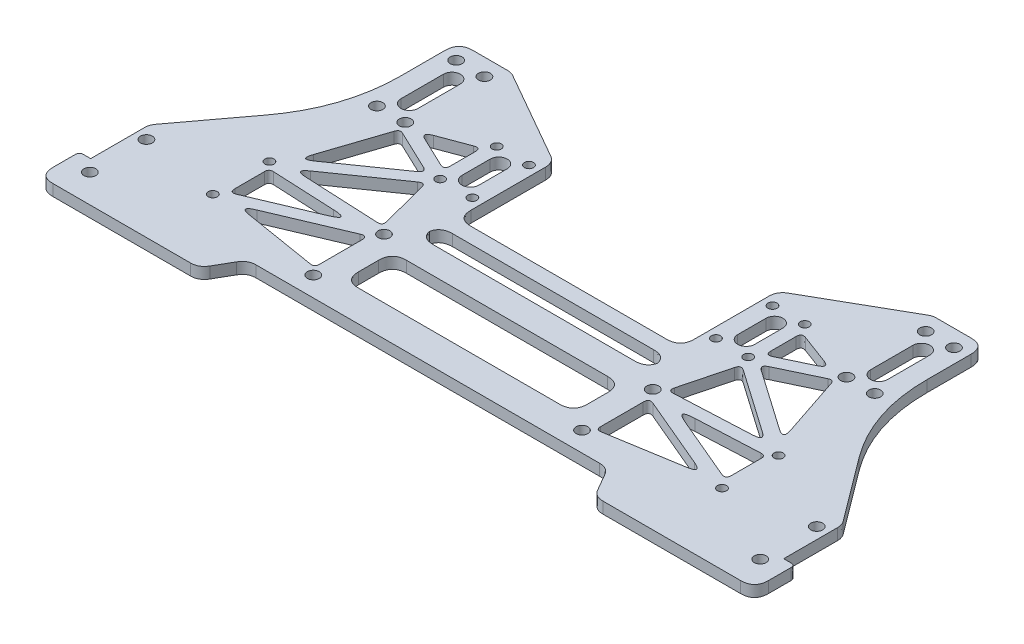
SolidWorks part; units mm, degrees
material "Hexcel AS4C (3000 丝)"
ref_plane "前视基准面" through (0, 0, 0) normal (0, 0, 1) x (1, 0, 0)
ref_plane "上视基准面" through (0, 0, 0) normal (0, 1, 0) x (1, 0, 0)
ref_plane "右视基准面" through (0, 0, 0) normal (1, 0, 0) x (0, 0, -1)
sketch "草图1" plane through (0, 0, 0) normal (0, 1, 0) x (1, 0, 0)
  line L0 (10, 0) -> (10, -115) construction
  line L1 (0, 0) -> (186, 0)
  line L2 (0, 0) -> (0, -115)
  line L3 (0, -115) -> (186, -115)
  line L4 (186, 0) -> (186, -115)
  line L5 (93, -115) -> (93, 0) construction
  line L6 (0, -57.5) -> (186, -57.5) construction
  line L7 (171, -6) -> (181, -6) construction
  line L8 (5, -6) -> (15, -6) construction
  line L9 (5, -6) -> (5, -34) construction
  line L10 (5, -34) -> (15, -34) construction
  line L11 (15, -6) -> (15, -34) construction
  line L12 (10, -34) -> (10, -6) construction
  line L13 (5, -20) -> (15, -20) construction
  line L14 (176, -6) -> (176, -50006) construction
  line L15 (10, -20) -> (-49990, -20) construction
  line L16 (93, -15) -> (93, -49864.2061) construction
  circle A6 centre (5, -6) radius 2.1
  circle A7 centre (15, -6) radius 2.1
  circle A8 centre (15, -34) radius 2.1
  circle A9 centre (5, -34) radius 2.1
  circle A10 centre (171, -34) radius 2.1
  circle A11 centre (181, -34) radius 2.1
  circle A12 centre (171, -6) radius 2.1
  circle A13 centre (181, -6) radius 2.1
  circle A14 centre (93, 120) radius 112.5 construction
  point P6 (10, -20)
  point P24 (176, -6)
  point P84 (93, -57.5)
  dimension "D4" = 10
  dimension "D7" = 4.2
  dimension "D8" = 225
  dimension "D1" = 115
  dimension "D2" = 186
  dimension "D3" = 10
  dimension "D6" = 20
  dimension "D5" = 28
  dimension "D9" = 140
extrude "凸台-拉伸1" add sketch "草图1" along normal blind 4
sketch "草图2" plane through (0, 4, 0) normal (0, 1, 0) x (1, 0, 0)
  line L0 (93, 0) -> (93, -50000) construction
  line L1 (186, 0) -> (0, 0) construction
  line L2 (0, -115) -> (186, -115) construction
  line L3 (45.5, -72) -> (140.5, -72) construction
  line L4 (45.5, -72) -> (45.5, -97) construction
  line L5 (45.5, -97) -> (140.5, -97) construction
  line L6 (140.5, -72) -> (140.5, -97) construction
  line L7 (93, -97) -> (93, -72) construction
  line L8 (45.5, -84.5) -> (140.5, -84.5) construction
  circle A0 centre (45.5, -72) radius 2.1
  circle A1 centre (45.5, -97) radius 2.1
  circle A2 centre (140.5, -97) radius 2.1
  circle A3 centre (140.5, -72) radius 2.1
  point P4 (93, 0)
  point P5 (93, -84.5)
  dimension "D4" = 4.2
  dimension "D1" = 95
  dimension "D2" = 25
  dimension "D3" = 18
extrude "切除-拉伸1" cut sketch "草图2" against normal through all
sketch "草图3" plane through (0, 4, 0) normal (0, 1, 0) x (1, 0, 0)
  line L0 (93, -60) -> (93, -50060) construction
  line L1 (0, -115) -> (186, -115) construction
  line L2 (23, -115) -> (29.3509, -104)
  line L3 (29.3509, -104) -> (156.6491, -104)
  line L4 (23, -115) -> (163, -115)
  line L5 (163, -115) -> (156.6491, -104)
  point P4 (93, -115)
  point P10 (93, -115)
  point P11 (93, -104)
  dimension "D1" = 11
  dimension "D2" = 70
  dimension "D3" = 60
extrude "切除-拉伸2" cut sketch "草图3" against normal through all
sketch "草图4" plane through (0, 4, 0) normal (0, 1, 0) x (1, 0, 0)
  line L0 (26.4641, -109) -> (0, -109)
  line L2 (29.3509, -104) -> (23, -115) construction
  line L3 (0, 0) -> (0, -115) construction
  line L4 (0, -109) -> (0, -115)
  line L5 (0, -115) -> (23, -115)
  line L6 (23, -115) -> (26.4641, -109)
  line L7 (93, -45) -> (93, -50045) construction
  line L8 (156.6491, -104) -> (29.3509, -104) construction
  line L9 (186, -115) -> (163, -115)
  line L10 (186, -109) -> (186, -115)
  line L11 (159.5359, -109) -> (186, -109)
  line L12 (163, -115) -> (159.5359, -109)
  point P14 (93, -104)
  dimension "D1" = 6
sketch "草图6" plane through (0, 4, 0) normal (0, 1, 0) x (1, 0, 0)
  line L0 (92.8983, 30) -> (-49907.1017, 30) construction
  line L1 (186, 0) -> (0, 0) construction
  line L2 (93, 0) -> (93, -50000) construction
  line L3 (129.6, -44.2) -> (56.4, -44.2)
  line L4 (56.4, 1) -> (129.6, 1)
  line L5 (56.4, 1) -> (56.4, -44.2)
  line L6 (56.4, -44.2) -> (129.6, -44.2) construction
  line L7 (129.6, 1) -> (129.6, -44.2)
  line L8 (93, -44.2) -> (93, 1) construction
  line L9 (56.4, -21.6) -> (129.6, -21.6) construction
  line L10 (49.95, -25.2) -> (147.45, -25.2) construction
  line L11 (49.95, -25.2) -> (49.95, -45.2) construction
  line L12 (49.95, -45.2) -> (147.45, -45.2) construction
  line L13 (147.45, -25.2) -> (147.45, -45.2) construction
  line L14 (98.7, -45.2) -> (98.7, -25.2) construction
  line L15 (49.95, -35.2) -> (147.45, -35.2) construction
  circle A0 centre (49.95, -45.2) radius 1.6
  circle A1 centre (49.95, -25.2) radius 1.6
  circle A2 centre (147.45, -45.2) radius 1.6
  circle A3 centre (147.45, -25.2) radius 1.6
  circle A4 centre (136.05, -45.2) radius 1.6
  circle A5 centre (136.05, -25.2) radius 1.6
  circle A6 centre (38.55, -45.2) radius 1.6
  circle A7 centre (38.55, -25.2) radius 1.6
  point P6 (93, 0)
  point P7 (93, -21.6)
  point P11 (98.7, -35.2)
  dimension "D9" = 3.2
  dimension "D1" = 30
  dimension "D2" = 45.2
  dimension "D3" = 73.2
  dimension "D4" = 29
  dimension "D5" = 1
  dimension "D6" = 6.45
  dimension "D7" = 17.85
  dimension "D8" = 20
extrude "切除-拉伸4" cut sketch "草图6" against normal through all
sketch "草图10" plane through (0, 4, 0) normal (0, 1, 0) x (1, 0, 0)
  line L0 (93, -30.2) -> (93, -50030.2) construction
  line L1 (56.4, -44.2) -> (129.6, -44.2) construction
  line L2 (56.4, 0) -> (0, 0) construction
  line L3 (53.5, 0) -> (132.5, 0)
  line L4 (53.5, 0) -> (53.5, -54.2)
  line L5 (53.5, -54.2) -> (132.5, -54.2)
  line L6 (132.5, 0) -> (132.5, -54.2)
  line L7 (93, -54.2) -> (93, 0) construction
  line L8 (53.5, -27.1) -> (132.5, -27.1) construction
  point P4 (93, -44.2)
  point P5 (93, -27.1)
  dimension "D1" = 79
  dimension "D2" = 10
extrude "切除-拉伸6" cut sketch "草图10" against normal through all
sketch "草图12" plane through (0, 4, 0) normal (0, 1, 0) x (1, 0, 0)
  line L0 (93, -104) -> (93, -50104) construction
  line L1 (0, -115) -> (-33.5, -115)
  line L2 (0, -115) -> (0, -80)
  line L3 (0, -80) -> (-33.5, -80)
  line L4 (-33.5, -115) -> (-33.5, -80)
  line L5 (-16.75, -80) -> (-16.75, -115) construction
  line L6 (0, -97.5) -> (-33.5, -97.5) construction
  line L7 (156.6491, -104) -> (29.3509, -104) construction
  line L8 (186, -80) -> (219.5, -80)
  line L9 (219.5, -115) -> (219.5, -80)
  line L10 (186, -115) -> (219.5, -115)
  line L11 (186, -115) -> (186, -80)
  point P8 (93, -104)
  point P148 (-16.75, -97.5)
  dimension "D1" = 35
  dimension "33.5" = 33.5
extrude "凸台-拉伸3" add sketch "草图12" against normal up to surface (4 mm away) up to face at (49.95, 0, 46.8)
sketch "草图13" plane through (0, 4, 0) normal (0, 1, 0) x (1, 0, 0)
  line L0 (93, -104) -> (93, -50104) construction
  line L1 (-33.5, -80) -> (-29.5, -80)
  line L2 (-33.5, -80) -> (-33.5, -100.7)
  line L3 (-33.5, -100.7) -> (-29.5, -100.7)
  line L4 (-29.5, -80) -> (-29.5, -100.7)
  line L5 (-31.5, -100.7) -> (-31.5, -80) construction
  line L6 (-33.5, -90.35) -> (-29.5, -90.35) construction
  line L7 (156.6491, -104) -> (29.3509, -104) construction
  line L8 (219.5, -100.7) -> (215.5, -100.7)
  line L9 (215.5, -80) -> (215.5, -100.7)
  line L10 (219.5, -80) -> (215.5, -80)
  line L11 (219.5, -80) -> (219.5, -100.7)
  point P8 (93, -104)
  point P124 (-31.5, -90.35)
  dimension "D1" = 20.7
  dimension "4" = 4
extrude "切除-拉伸7" cut sketch "草图13" against normal through all
sketch "草图14" plane through (0, 4, 0) normal (0, 1, 0) x (1, 0, 0)
  line L0 (-29.5, -80) -> (0, -40.5)
  line L1 (0, 0) -> (0, -115) construction
  line L2 (0, -40.5) -> (0, -80)
  line L3 (0, -80) -> (-29.5, -80)
  line L4 (93, -104) -> (93, -50050.2158) construction
  line L5 (156.6491, -104) -> (29.3509, -104) construction
  line L7 (186, -40.5) -> (186, -80)
  line L8 (215.5, -80) -> (186, -40.5)
  line L9 (186, -80) -> (215.5, -80)
  point P11 (93, -104)
  dimension "D1" = 39.5
extrude "凸台-拉伸4" add sketch "草图14" against normal up to surface (4 mm away) up to face at (49.95, 0, 46.8)
sketch "草图15" plane through (0, 4, 0) normal (0, 1, 0) x (1, 0, 0)
  line L0 (0, -40.5) -> (0, -50040.5) construction
  line L1 (3, -47.7433) -> (3, -50047.7433) construction
  line L2 (3, -90) -> (3, -70) construction
  line L3 (-33.5, -115) -> (23, -115) construction
  line L4 (93, -54.2) -> (93, -50054.2) construction
  line L5 (53.5, -54.2) -> (132.5, -54.2) construction
  circle A0 centre (3, -90) radius 1.6
  circle A1 centre (3, -70) radius 1.6
  circle A2 centre (183, -90) radius 1.6
  circle A3 centre (183, -70) radius 1.6
  point P17 (93, -54.2)
  dimension "D2" = 3.2
  dimension "D1" = 3
  dimension "D4" = 20
  dimension "D5" = 25
  dimension "D3" = 2
extrude "切除-拉伸8" cut sketch "草图15" against normal through all
sketch "草图16" plane through (0, 4, 0) normal (0, 1, 0) x (1, 0, 0)
  line L0 (93, -104) -> (93, -50104) construction
  line L1 (156.6491, -104) -> (29.3509, -104) construction
  line L2 (18.5, 0) -> (53.5, 0)
  line L3 (53.5, 0) -> (0, 0) construction
  line L4 (53.5, 0) -> (53.5, -20)
  line L5 (53.5, 0) -> (53.5, -54.2) construction
  line L6 (53.5, -20) -> (18.5, 0)
  line L7 (132.5, 0) -> (132.5, -20)
  line L8 (167.5, 0) -> (132.5, 0)
  line L9 (132.5, -20) -> (167.5, 0)
  line L11 (5, -6) -> (15, -6) construction
  line L16 (5, -6) -> (5, -34) construction
  line L17 (5, -34) -> (15, -34) construction
  line L18 (15, -6) -> (15, -34) construction
  line L19 (10, -12.5) -> (10, -27.5) construction
  line L20 (13, -12.5) -> (13, -27.5)
  line L26 (7, -12.5) -> (7, -27.5)
  line L27 (5, -20) -> (15, -20) construction
  line L30 (44.25, -30.2) -> (44.25, -40.2) construction
  line L31 (45.5, -72) -> (140.5, -72) construction
  line L32 (45.5, -72) -> (45.5, -97) construction
  line L33 (45.5, -97) -> (140.5, -97) construction
  line L34 (140.5, -72) -> (140.5, -97) construction
  line L35 (93, -97) -> (93, -72) construction
  line L36 (45.5, -84.5) -> (140.5, -84.5) construction
  line L37 (52.5, -76) -> (133.5, -76)
  line L38 (52.5, -76) -> (52.5, -93)
  line L39 (52.5, -93) -> (133.5, -93)
  line L40 (133.5, -76) -> (133.5, -93)
  line L41 (93, -93) -> (93, -76) construction
  line L42 (52.5, -84.5) -> (133.5, -84.5) construction
  line L43 (38.55, -25.2) -> (49.95, -25.2) construction
  line L44 (38.55, -25.2) -> (38.55, -45.2) construction
  line L45 (38.55, -45.2) -> (49.95, -45.2) construction
  line L46 (49.95, -25.2) -> (49.95, -45.2) construction
  line L47 (44.25, -45.2) -> (44.25, -25.2) construction
  line L48 (38.55, -35.2) -> (49.95, -35.2) construction
  line L49 (47.25, -30.2) -> (47.25, -40.2)
  line L50 (41.25, -30.2) -> (41.25, -40.2)
  line L51 (141.75, -30.2) -> (141.75, -40.2) construction
  line L52 (138.75, -30.2) -> (138.75, -40.2)
  line L53 (144.75, -30.2) -> (144.75, -40.2)
  line L54 (53.5, -54.2) -> (132.5, -54.2) construction
  line L55 (52.5, -59.7) -> (133.5, -59.7)
  line L56 (52.5, -59.7) -> (52.5, -66.5)
  line L57 (52.5, -66.5) -> (133.5, -66.5)
  line L58 (133.5, -59.7) -> (133.5, -66.5)
  line L59 (93, -66.5) -> (93, -59.7) construction
  line L60 (52.5, -63.1) -> (133.5, -63.1) construction
  line L61 (176, -12.5) -> (176, -27.5) construction
  line L62 (173, -12.5) -> (173, -27.5)
  line L63 (179, -12.5) -> (179, -27.5)
  arc A0 (47.25, -30.2) -> (41.25, -30.2) centre (44.25, -30.2) ccw
  arc A1 (41.25, -40.2) -> (47.25, -40.2) centre (44.25, -40.2) ccw
  arc A2 (138.75, -30.2) -> (144.75, -30.2) centre (141.75, -30.2) cw
  arc A3 (144.75, -40.2) -> (138.75, -40.2) centre (141.75, -40.2) cw
  arc A4 (13, -12.5) -> (7, -12.5) centre (10, -12.5) ccw
  arc A5 (7, -27.5) -> (13, -27.5) centre (10, -27.5) ccw
  arc A6 (173, -12.5) -> (179, -12.5) centre (176, -12.5) cw
  arc A7 (179, -27.5) -> (173, -27.5) centre (176, -27.5) cw
  point P4 (93, -104)
  point P21 (10, -20)
  point P24 (10, -20)
  point P32 (93, -84.5)
  point P42 (44.25, -35.2)
  point P49 (141.75, -35.2)
  point P54 (93, -63.1)
  point P72 (176, -20)
  point P308 (10, -20)
  point P312 (44.25, -35.2)
  point P432 (93, -84.5)
  dimension "D8" = 3
  dimension "D4" = 3
  dimension "D1" = 35
  dimension "D2" = 20
  dimension "D3" = 15
  dimension "D5" = 4
  dimension "D6" = 7
  dimension "D7" = 10
  dimension "D9" = 5.5
  dimension "D10" = 9.5
extrude "切除-拉伸9" cut sketch "草图16" against normal through all
sketch "草图17" plane through (0, 4, 0) normal (0, 1, 0) x (1, 0, 0)
  line L0 (93, -104) -> (93, -50104) construction
  line L1 (156.6491, -104) -> (29.3509, -104) construction
  line L2 (45.5, -97) -> (3, -90) construction
  line L3 (3, -90) -> (45.5, -72) construction
  line L4 (45.5, -72) -> (3, -70) construction
  line L5 (3, -70) -> (38.55, -45.2) construction
  line L6 (38.55, -45.2) -> (15, -34) construction
  line L7 (15, -34) -> (3, -70) construction
  line L8 (3, -70) -> (3, -90) construction
  line L9 (45.5, -97) -> (45.5, -72) construction
  line L10 (45.5, -72) -> (38.55, -45.2) construction
  line L11 (43.3, -94.408) -> (10.852, -89.0636)
  line L12 (10.852, -89.0636) -> (43.3, -75.3209)
  line L13 (43.3, -94.408) -> (43.3, -75.3209)
  line L14 (5.2, -86.6791) -> (35.7428, -73.7433)
  line L15 (35.7428, -73.7433) -> (5.2, -72.306)
  line L16 (5.2, -72.306) -> (5.2, -86.6791)
  line L17 (42.6209, -69.6621) -> (9.5598, -68.1063)
  line L18 (9.5598, -68.1063) -> (37.2145, -48.8141)
  line L19 (42.6209, -69.6621) -> (37.2145, -48.8141)
  line L20 (7.1867, -64.3969) -> (34.1871, -45.5612)
  line L21 (34.1871, -45.5612) -> (16.3008, -37.0547)
  line L22 (16.3008, -37.0547) -> (7.1867, -64.3969)
  line L23 (142.7, -94.408) -> (142.7, -75.3209)
  line L24 (175.148, -89.0636) -> (142.7, -75.3209)
  line L25 (142.7, -94.408) -> (175.148, -89.0636)
  line L26 (180.8, -72.306) -> (180.8, -86.6791)
  line L27 (150.2572, -73.7433) -> (180.8, -72.306)
  line L28 (180.8, -86.6791) -> (150.2572, -73.7433)
  line L29 (143.3791, -69.6621) -> (148.7855, -48.8141)
  line L30 (176.4402, -68.1063) -> (148.7855, -48.8141)
  line L31 (143.3791, -69.6621) -> (176.4402, -68.1063)
  line L32 (169.6992, -37.0547) -> (178.8133, -64.3969)
  line L33 (151.8129, -45.5612) -> (169.6992, -37.0547)
  line L34 (178.8133, -64.3969) -> (151.8129, -45.5612)
  line L35 (15, -34) -> (15, -6) construction
  line L36 (15, -6) -> (38.55, -25.2) construction
  line L37 (15, -34) -> (38.55, -25.2) construction
  line L38 (38.55, -25.2) -> (38.55, -45.2) construction
  line L39 (20.634, -34.2433) -> (36.35, -28.3707)
  line L40 (36.35, -28.3707) -> (36.35, -41.7176)
  line L41 (36.35, -41.7176) -> (20.634, -34.2433)
  line L42 (149.65, -41.7176) -> (165.366, -34.2433)
  line L43 (149.65, -28.3707) -> (149.65, -41.7176)
  line L44 (165.366, -34.2433) -> (149.65, -28.3707)
  point P4 (93, -104)
  dimension "D1" = 2.2
  dimension "D2" = 2.2
  dimension "D3" = 2.2
  dimension "D4" = 2.2
  dimension "D5" = 2.2
extrude "切除-拉伸10" cut sketch "草图17" against normal through all
fillet "圆角1" radius 1.5 32 edges at (149.65, 2, 28.3707) (165.366, 2, 34.2433) (149.65, 2, 41.7176) (169.6992, 2, 37.0547) (178.8133, 2, 64.3969) (151.8129, 2, 45.5612) (148.7855, 2, 48.8141) (143.3791, 2, 69.6621) (176.4402, 2, 68.1063) (180.8, 2, 86.6791) (180.8, 2, 72.306) (150.2572, 2, 73.7433) (142.7, 2, 75.3209) (175.148, 2, 89.0636) (142.7, 2, 94.408) (43.3, 2, 75.3209) (43.3, 2, 94.408) (10.852, 2, 89.0636) (35.7428, 2, 73.7433) (5.2, 2, 86.6791) (5.2, 2, 72.306) (37.2145, 2, 48.8141) (42.6209, 2, 69.6621) (9.5598, 2, 68.1063) (7.1867, 2, 64.3969) (16.3008, 2, 37.0547) (34.1871, 2, 45.5612) (36.35, 2, 41.7176) (36.35, 2, 28.3707) (20.634, 2, 34.2433) (-33.5, 2, 100.7) (219.5, 2, 100.7) conic rho 0.5
fillet "圆角2" radius 5 24 edges at (23, 2, 115) (29.3509, 2, 104) (156.6491, 2, 104) (163, 2, 115) (219.5, 2, 115) (-33.5, 2, 115) (-29.5, 2, 80) (215.5, 2, 80) (0, 2, 0) (18.5, 2, 0) (53.5, 2, 20) (53.5, 2, 54.2) (186, 2, 0) (167.5, 2, 0) (132.5, 2, 20) (132.5, 2, 54.2) (133.5, 2, 66.5) (133.5, 2, 59.7) (52.5, 2, 59.7) (52.5, 2, 66.5) (52.5, 2, 76) (133.5, 2, 76) (133.5, 2, 93) (52.5, 2, 93) conic rho 0.5
sketch "草图18" plane through (0, 4, 0) normal (0, 1, 0) x (1, 0, 0)
  line L0 (-25.5, -74.6441) -> (-25.5, -115) construction
  line L1 (0, -40.5) -> (-28.5061, -78.6692) construction
  line L2 (-28.5, -115) -> (20.1132, -115) construction
  line L3 (-29.5, -100.7) -> (-29.5, -81.661) construction
  line L4 (93, -104) -> (93, -50104) construction
  line L5 (153.7624, -104) -> (32.2376, -104) construction
  circle A0 centre (-25.5, -105) radius 2.1
  circle A1 centre (-25.5, -85) radius 2.1
  circle A2 centre (211.5, -85) radius 2.1
  circle A3 centre (211.5, -105) radius 2.1
  point P16 (93, -104)
  dimension "D2" = 4.2
  dimension "D1" = 4
  dimension "D3" = 20
  dimension "9.71" = 10
extrude "切除-拉伸11" cut sketch "草图18" against normal through all
fillet "圆角3" radius 60 2 edges at (0, 2, 40.5) (186, 2, 40.5) conic rho 0.5
fillet "圆角4" radius 0.1 2 edges at (215.5, 2, 100.7) (-29.5, 2, 100.7) conic rho 0.5
